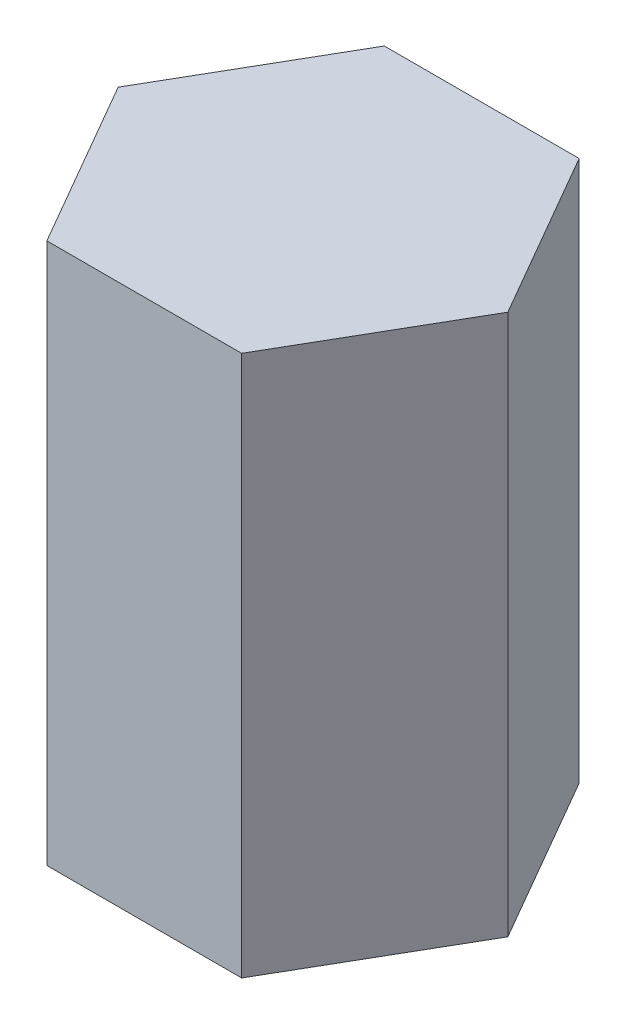
SolidWorks part; units mm, degrees
other "Markup1"
sketch "Sketch4" plane through (577.3503, 1603, 500) normal (0.5856, 0.3664, 0.723) x (0.7705, 0.0254, -0.6369)
material "Bus"
ref_plane "Front Plane" through (0, 0, 0) normal (0, 0, 1) x (1, 0, 0)
ref_plane "Top Plane" through (0, 0, 0) normal (0, 1, 0) x (1, 0, 0)
ref_plane "Right Plane" through (0, 0, 0) normal (1, 0, 0) x (0, 0, -1)
sketch "Sketch2" plane through (0, 0, 0) normal (0, 1, 0) x (1, 0, 0)
  line L1 (577.3503, 0) -> (288.6751, 500)
  line L2 (288.6751, 500) -> (-288.6751, 500)
  line L3 (-288.6751, 500) -> (-577.3503, 0)
  line L4 (-577.3503, 0) -> (-288.6751, -500)
  line L5 (-288.6751, -500) -> (288.6751, -500)
  line L6 (288.6751, -500) -> (577.3503, 0)
  circle A0 centre (0, 0) radius 500 construction
  dimension "D1" = 1000
extrude "Boss-Extrude1" add sketch "Sketch2" along normal blind 1603
ref_axis "Axis1" through (0, -313.0569, 0) along (0, 1, 0)
ref_plane "Plane2" through (0, 400.75, 0) normal (0, 1, 0) x (1, 0, 0)
sketch "Sketch3" plane through (0, 400.75, 0) normal (0, 1, 0) x (1, 0, 0)
  line L0 (288.6751, 500) -> (-288.6751, 500) construction
  line L1 (575.0409, 0) -> (287.5204, 498)
  line L2 (287.5204, 498) -> (-287.5204, 498)
  line L3 (-287.5204, 498) -> (-575.0409, 0)
  line L4 (-575.0409, 0) -> (-287.5204, -498)
  line L5 (-287.5204, -498) -> (287.5204, -498)
  line L6 (287.5204, -498) -> (575.0409, 0)
  circle A0 centre (0, 0) radius 498 construction
  dimension "D1" = 996
extrude "Cut-Extrude1" cut sketch "Sketch3" along normal blind 1187.25
